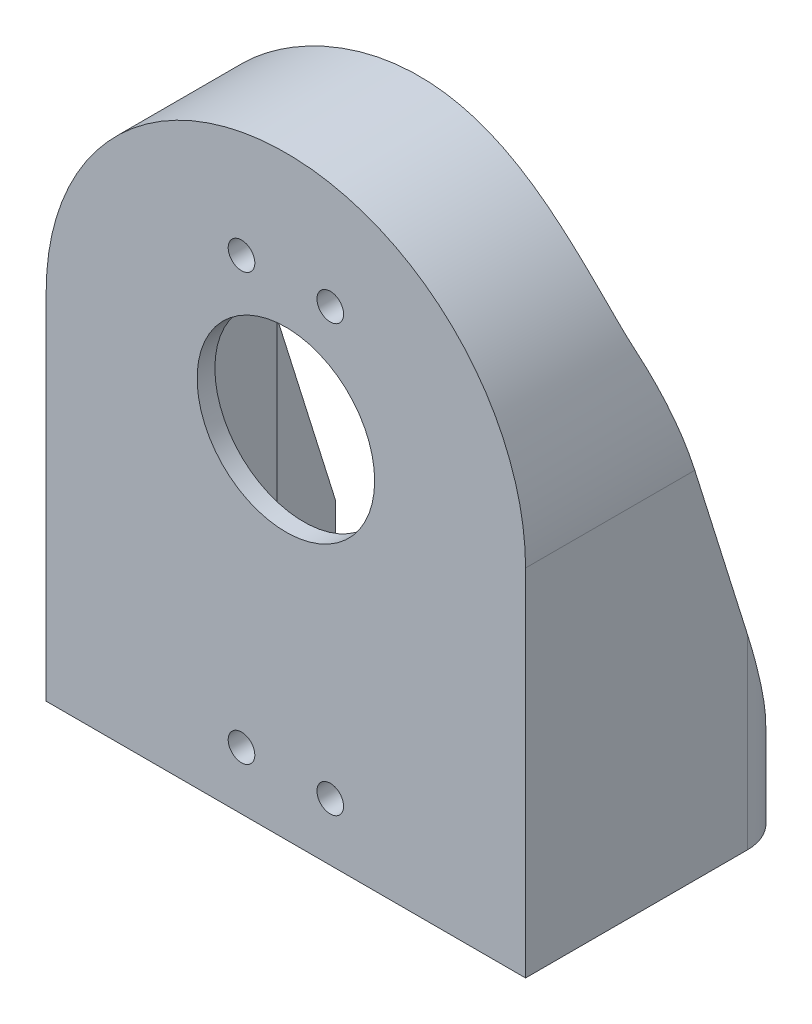
SolidWorks part; units mm, degrees
material "ABS"
ref_plane "Front Plane" through (0, 0, 0) normal (0, 0, 1) x (1, 0, 0)
ref_plane "Top Plane" through (0, 0, 0) normal (0, 1, 0) x (1, 0, 0)
ref_plane "Right Plane" through (0, 0, 0) normal (1, 0, 0) x (0, 0, -1)
sketch "Sketch3" plane through (0, 0, 0) normal (0, 0, 1) x (1, 0, 0)
  line L0 (-24, -17) -> (24, -17)
  line L1 (-27, -20) -> (27, -20)
  line L2 (-27, -20) -> (-27, 20)
  line L4 (27, -20) -> (27, 20)
  line L5 (-27, -20) -> (27, 20) construction
  line L6 (-27, 20) -> (27, -20) construction
  line L7 (24, -17) -> (24, 20)
  line L8 (-24, -17) -> (-24, 20)
  arc A0 (-27, 20) -> (27, 20) centre (0, 20) cw
  circle A1 centre (0, 20) radius 10
  arc A2 (-24, 20) -> (24, 20) centre (0, 20) cw
  point P0 (0, 0)
  dimension "D2" = 54
  dimension "D3" = 27
  dimension "D4" = 20
  dimension "D1" = 40
  dimension "D5" = 3
extrude "Boss-Extrude1" add sketch "Sketch3" against normal blind 30 contours A0 L2 L1 L4 L8 A2 L7 L0 region at (-26.1395, 0, 0)
extrude "Boss-Extrude2" add sketch "Sketch3<4>" against normal blind 10 contours A2 L8 L0 L7 A1 region at (-23.2238, 1.5, 0)
sketch "Sketch3<4>" plane through (0, 0, 0) normal (0, 0, 1) x (1, 0, 0) same geometry as "Sketch3"
sketch "Sketch4" plane through (0, -20, 0) normal (0, -1, 0) x (1, 0, 0)
  line L0 (-27, 0) -> (27, 0) construction
  line L1 (27, -30) -> (27, 0) construction
  circle A0 centre (10, -15) radius 10 construction
  circle A1 centre (3, -15) radius 1.5
  circle A2 centre (17, -15) radius 1.5
  circle A3 centre (10, -15) radius 2
  dimension "D1" = 20
  dimension "D4" = 3
  dimension "D5" = 3
  dimension "D6" = 7
  dimension "D10" = 4
  dimension "D2" = 15
  dimension "D3" = 17
  dimension "D7" = 7
  dimension "D8" = 15
  dimension "D9" = 15
extrude "Cut-Extrude1" cut sketch "Sketch4" against normal blind 10 contours A1 | A2 | A3
sketch "Sketch5" plane through (0, 0, 0) normal (1, 0, 0) x (0, 0, -1)
  line L3 (15.255, 32.1839) -> (30, -15)
  line L4 (30, -20) -> (30, 20) construction
  line L5 (0, 47) -> (0, 20) construction
  line L6 (30, 47) -> (0, 47) construction
  line L7 (15, 47) -> (30, 47)
  line L8 (30, 47) -> (30, -15)
  arc A0 (14.6901, 34.4482) -> (15, 47) centre (44.1719, 40) cw
  arc A1 (15.255, 32.1839) -> (14.6901, 34.4482) centre (34.3446, 38.1494) cw
  point P16 (15, 33)
  dimension "D2" = 14
  dimension "D4" = 30
  dimension "D5" = 20
  dimension "D1" = 5
  dimension "D3" = 15
extrude "Cut-Extrude2" cut sketch "Sketch5" against normal through all both and the other way through all
sketch "Sketch6" plane through (0, 0, -10) normal (0, 0, -1) x (-1, 0, 0)
  line L0 (-11, 10.5) -> (11, 10.5) construction
  line L1 (-11, 31) -> (11, 31)
  line L2 (-11, 31) -> (-11, -10)
  line L3 (-11, -10) -> (11, -10)
  line L4 (11, 31) -> (11, -10)
  line L5 (-11, 31) -> (11, -10) construction
  line L6 (-11, -10) -> (11, 31) construction
  circle A0 centre (-5, 34.5) radius 1.5
  circle A1 centre (5, 34.5) radius 1.5
  circle A2 centre (5, -13.5) radius 1.5
  circle A3 centre (-5, -13.5) radius 1.5
  point P4 (0, 10.5)
  point P9 (0, 20)
  circle M8 centre (0, 20) radius 10
  dimension "D4" = 3
  dimension "D1" = 41
  dimension "D2" = 22
  dimension "D3" = 11
  dimension "D5" = 3.5
  dimension "D6" = 10
  dimension "D7" = 6
extrude "Cut-Extrude3" cut sketch "Sketch6" against normal blind 8 contours L4 L1 L2 L3 M8 region at (0, 5.4229, -10)
extrude "Cut-Extrude4" cut sketch "Sketch6<3>" against normal through all contours A3 | A2 | A0 | A1
sketch "Sketch6<3>" plane through (0, 0, -10) normal (0, 0, -1) x (-1, 0, 0) same geometry as "Sketch6"
sketch "Sketch7" plane through (0, -20, 0) normal (0, -1, 0) x (1, 0, 0)
  line L0 (-27, -25) -> (-27, -30)
  line L1 (-27, -30) -> (-22, -30)
  line L2 (22, -30) -> (27, -30)
  line L3 (27, -30) -> (27, -25)
  arc A0 (22, -30) -> (27, -25) centre (22, -25) ccw
  arc A1 (-27, -25) -> (-22, -30) centre (-22, -25) ccw
  dimension "D2" = 5
extrude "Cut-Extrude5" cut sketch "Sketch7" against normal through all
